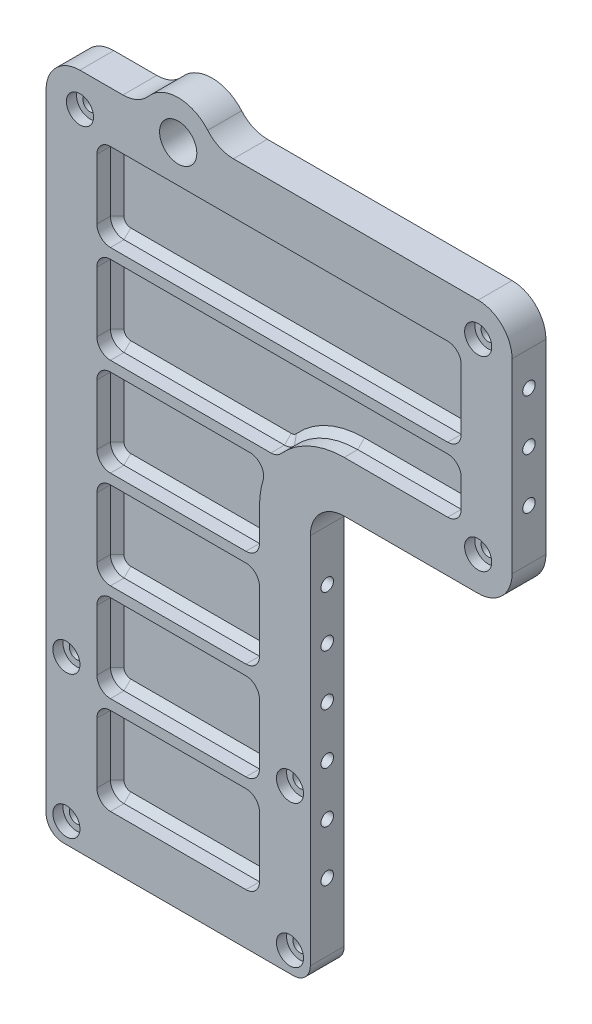
SolidWorks part; units mm, degrees
material "Petg 30% Infill"
ref_plane "Front Plane" through (0, 0, 0) normal (0, 0, 1) x (1, 0, 0)
ref_plane "Top Plane" through (0, 0, 0) normal (0, 1, 0) x (1, 0, 0)
ref_plane "Right Plane" through (0, 0, 0) normal (1, 0, 0) x (0, 0, -1)
sketch "Sketch1" plane through (0, 0, 0) normal (0, 0, 1) x (1, 0, 0)
  line L11 (-3.4368, 12.7092) -> (-3.4368, 122.7092)
  line L12 (6.5632, 132.7092) -> (46.1195, 132.7092)
  line L13 (56.1195, 142.7092) -> (56.1195, 197.7092)
  line L14 (46.1195, 207.7092) -> (-26.1197, 207.7092)
  line L15 (-58.754, 207.7092) -> (-71.4368, 207.7092)
  line L16 (-81.4368, 197.7092) -> (-81.4368, 12.7092)
  line L17 (-76.4368, 7.7092) -> (-8.4368, 7.7092)
  line L18 (-3.4368, 12.7092) -> (-3.4368, 122.7092)
  line L19 (6.5632, 132.7092) -> (46.1195, 132.7092)
  line L20 (56.1195, 142.7092) -> (56.1195, 197.7092)
  line L21 (46.1195, 207.7092) -> (-26.1197, 207.7092)
  line L22 (-58.754, 207.7092) -> (-71.4368, 207.7092)
  line L23 (-81.4368, 197.7092) -> (-81.4368, 12.7092)
  line L24 (-76.4368, 7.7092) -> (-8.4368, 7.7092)
  circle A0 centre (-42.4368, 203.7092) radius 5.5
  arc A1 (-3.4368, 12.7092) -> (-8.4368, 7.7092) centre (-8.4368, 12.7092) cw
  arc A2 (-81.4368, 12.7092) -> (-76.4368, 7.7092) centre (-76.4368, 12.7092) ccw
  circle A3 centre (-42.4368, 203.7092) radius 5.5 construction
  circle A4 centre (-75.4368, 55.7092) radius 2.15
  circle A5 centre (-75.4368, 13.7092) radius 2.15
  circle A6 centre (-9.4368, 13.7092) radius 2.15
  arc A7 (6.5632, 132.7092) -> (-3.4368, 122.7092) centre (6.5632, 122.7092) ccw
  arc A8 (46.1195, 132.7092) -> (56.1195, 142.7092) centre (46.1195, 142.7092) ccw
  arc A9 (56.1195, 197.7092) -> (46.1195, 207.7092) centre (46.1195, 197.7092) ccw
  arc A10 (-33.709, 211.1975) -> (-26.1197, 207.7092) centre (-26.1197, 217.7092) ccw
  arc A11 (-33.709, 211.1975) -> (-51.1646, 211.1975) centre (-42.4368, 203.7092) ccw
  arc A12 (-58.754, 207.7092) -> (-51.1646, 211.1975) centre (-58.754, 217.7092) ccw
  arc A13 (-71.4368, 207.7092) -> (-81.4368, 197.7092) centre (-71.4368, 197.7092) ccw
  arc A14 (6.5632, 132.7092) -> (-3.4368, 122.7092) centre (6.5632, 122.7092) ccw
  arc A15 (46.1195, 132.7092) -> (56.1195, 142.7092) centre (46.1195, 142.7092) ccw
  arc A16 (56.1195, 197.7092) -> (46.1195, 207.7092) centre (46.1195, 197.7092) ccw
  arc A17 (-33.709, 211.1975) -> (-26.1197, 207.7092) centre (-26.1197, 217.7092) ccw
  arc A18 (-33.709, 211.1975) -> (-51.1646, 211.1975) centre (-42.4368, 203.7092) ccw
  arc A19 (-58.754, 207.7092) -> (-51.1646, 211.1975) centre (-58.754, 217.7092) ccw
  arc A20 (-71.4368, 207.7092) -> (-81.4368, 197.7092) centre (-71.4368, 197.7092) ccw
  circle A21 centre (-9.4368, 55.7092) radius 2.15
  circle A23 centre (-75.4368, 13.7092) radius 2.2 construction
  circle A24 centre (-75.4368, 55.7092) radius 2.2 construction
  circle A25 centre (-9.4368, 13.7092) radius 2.2 construction
  circle A26 centre (-9.4368, 55.7092) radius 2.2 construction
  arc A35 (-81.4368, 12.7092) -> (-76.4368, 7.7092) centre (-76.4368, 12.7092) ccw
  arc A36 (-81.4368, 12.7092) -> (-76.4368, 7.7092) centre (-76.4368, 12.7092) ccw
  arc A37 (-8.4368, 7.7092) -> (-3.4368, 12.7092) centre (-8.4368, 12.7092) ccw
  arc A38 (-8.4368, 7.7092) -> (-3.4368, 12.7092) centre (-8.4368, 12.7092) ccw
  dimension "D2" = 4.3
  dimension "D3" = 5
  dimension "D1" = 0
extrude "Boss-Extrude1" add sketch "Sketch1" along normal blind 10 contours A1 L18 A14 L19 A15 L20 A16 L21 A17 A18 A19 L22 A20 L23 A2 L24 | A0 | A21 | A6 | A4 | A5
sketch "Sketch2" plane through (0, 0, 10) normal (0, 0, 1) x (1, 0, 0)
  circle A0 centre (-75.4368, 55.7092) radius 4
  circle A1 centre (-9.4368, 55.7092) radius 4
  circle A2 centre (-9.4368, 13.7092) radius 4
  circle A3 centre (-75.4368, 13.7092) radius 4
  dimension "D1" = 8
extrude "Cut-Extrude1" cut sketch "Sketch2" against normal blind 3
sketch "Sketch3" plane through (0, 0, 0) normal (0, 0, -1) x (-1, 0, 0)
  circle A0 centre (-21.6596, 190.973) radius 1.85
  circle A1 centre (31.0338, 190.3381) radius 1.85
  circle A2 centre (-21.6596, 190.973) radius 4.85
  circle A3 centre (31.0338, 190.3381) radius 4.85
  dimension "D1" = 3.7
  dimension "D2" = 3
extrude "Boss-Extrude2" add sketch "Sketch3" along normal blind 4
sketch "Sketch5" plane through (0, 0, 0) normal (0, 0, -1) x (-1, 0, 0)
  line L0 (47.5919, 184.6852) -> (47.5919, 70.4633) construction
  line L1 (13.3104, 85.2357) -> (47.5919, 85.2357)
  line L2 (13.3104, 85.2357) -> (13.3104, 70.4633)
  line L3 (13.3104, 70.4633) -> (47.5919, 70.4633)
  line L4 (47.5919, 85.2357) -> (47.5919, 70.4633)
  line L5 (47.5919, 70.4633) -> (-38.9159, 70.4633) construction
extrude "Boss-Extrude3" add sketch "Sketch5" along normal blind 4
sketch "Sketch6" plane through (0, 0, 0) normal (0, 0, -1) x (-1, 0, 0)
  line L0 (13.7834, 69.9633) -> (13.7834, 65.6705)
  line L1 (13.7834, 65.6705) -> (52.3848, 65.6705)
  line L2 (52.3848, 65.6705) -> (52.3848, 97.0706)
  line L3 (52.3848, 97.0706) -> (48.0919, 97.0706)
  line L4 (48.0919, 97.0706) -> (48.0919, 69.9633)
  line L5 (48.0919, 69.9633) -> (13.7834, 69.9633)
  line L6 (13.3104, 70.4633) -> (47.5919, 70.4633) construction
  line L7 (47.5919, 70.4633) -> (47.5919, 85.2357) construction
  dimension "D1" = 0.5
  dimension "D2" = 0.5
extrude "Boss-Extrude4" add sketch "Sketch6" along normal blind 6
sketch "Sketch7" plane through (0, 0, -6) normal (0, 0, -1) x (-1, 0, 0)
  line L0 (52.3848, 97.0706) -> (46.0919, 97.0706)
  line L1 (46.0919, 97.0706) -> (46.0919, 71.9633)
  line L2 (46.0919, 71.9633) -> (13.7834, 71.9633)
  line L3 (13.7834, 71.9633) -> (13.7834, 65.6705)
  line L4 (13.7834, 65.6705) -> (52.3848, 65.6705)
  line L5 (52.3848, 65.6705) -> (52.3848, 97.0706)
  line L6 (48.0919, 69.9633) -> (13.7834, 69.9633) construction
  dimension "D1" = 2
extrude "Boss-Extrude5" add sketch "Sketch7" along normal blind 2
chamfer "Chamfer1" distance 2 angle 45 2 edges at (-46.0919, 84.517, -6) (-29.9377, 71.9633, -6)
sketch "Sketch9" plane through (0, 0, 10) normal (0, 0, 1) x (1, 0, 0)
  circle A0 centre (-71.4368, 197.7092) radius 2.15
  circle A1 centre (46.1195, 197.7092) radius 2.15
  arc A2 (56.1195, 197.7092) -> (46.1195, 207.7092) centre (46.1195, 197.7092) ccw construction
  arc A3 (-71.4368, 207.7092) -> (-81.4368, 197.7092) centre (-71.4368, 197.7092) ccw construction
  circle A4 centre (46.1195, 142.7092) radius 2.15
  arc A5 (46.1195, 132.7092) -> (56.1195, 142.7092) centre (46.1195, 142.7092) ccw construction
  dimension "D1" = 4.3
extrude "Cut-Extrude3" cut sketch "Sketch9" against normal blind 20
sketch "Sketch10" plane through (0, 0, 10) normal (0, 0, 1) x (1, 0, 0)
  circle A0 centre (-71.4368, 197.7092) radius 4
  circle A1 centre (46.1195, 197.7092) radius 4
  circle A2 centre (46.1195, 197.7092) radius 2.15 construction
  circle A3 centre (46.1195, 142.7092) radius 4
  arc A4 (46.1195, 132.7092) -> (56.1195, 142.7092) centre (46.1195, 142.7092) ccw construction
  dimension "D1" = 8
extrude "Cut-Extrude4" cut sketch "Sketch10" against normal blind 3
chamfer "Chamfer2" distance 4 angle 45 2 edges at (16.8096, 190.973, 0) (-35.8838, 190.3381, 0)
sketch "Sketch12" plane through (0, 0, 10) normal (0, 0, 1) x (1, 0, 0)
  line L0 (-62.4368, 166.8758) -> (37.1195, 166.8758)
  line L1 (-62.4368, 163.8758) -> (37.1195, 163.8758)
  line L2 (-62.4368, 135.0425) -> (-21.2137, 135.0425)
  line L3 (-62.4368, 138.0425) -> (-15.0522, 138.0425)
  line L4 (-62.4368, 106.2092) -> (-22.4368, 106.2092)
  line L5 (-62.4368, 109.2092) -> (-22.4368, 109.2092)
  line L6 (-62.4368, 77.3758) -> (-22.4368, 77.3758)
  line L7 (-62.4368, 80.3758) -> (-22.4368, 80.3758)
  line L8 (-62.4368, 48.5425) -> (-22.4368, 48.5425)
  line L9 (-62.4368, 51.5425) -> (-22.4368, 51.5425)
  line L10 (-66.4368, 44.5425) -> (-66.4368, 26.7092)
  line L11 (-18.4368, 55.5425) -> (-18.4368, 73.3758)
  line L12 (-18.4368, 84.3758) -> (-18.4368, 102.2092)
  line L13 (-66.4368, 73.3758) -> (-66.4368, 55.5425)
  line L14 (-66.4368, 22.7092) -> (-18.4368, 22.7092)
  line L15 (-18.4368, 22.7092) -> (-18.4368, 122.7092)
  line L16 (6.5632, 147.7092) -> (41.1195, 147.7092)
  line L17 (41.1195, 147.7092) -> (41.1195, 192.7092)
  line L18 (41.1195, 192.7092) -> (-26.1197, 192.7092)
  line L19 (-58.754, 192.7092) -> (-66.4368, 192.7092)
  line L20 (-66.4368, 192.7092) -> (-66.4368, 22.7092)
  line L21 (-62.4368, 22.7092) -> (-22.4368, 22.7092)
  line L22 (-18.4368, 26.7092) -> (-18.4368, 44.5425)
  line L23 (6.5632, 147.7092) -> (37.1195, 147.7092)
  line L24 (41.1195, 151.7092) -> (41.1195, 159.8758)
  line L26 (37.1195, 192.7092) -> (-62.4368, 192.7092)
  line L27 (-66.4368, 188.7092) -> (-66.4368, 170.8758)
  line L28 (-18.4368, 113.2092) -> (-18.4368, 122.7092)
  line L29 (-66.4368, 102.2092) -> (-66.4368, 84.3758)
  line L30 (-66.4368, 131.0425) -> (-66.4368, 113.2092)
  line L31 (-66.4368, 159.8758) -> (-66.4368, 142.0425)
  line L32 (41.1195, 170.8758) -> (41.1195, 188.7092)
  line L33 (-38.7787, 192.7092) -> (-38.7787, 166.8758) construction
  line L34 (-38.7787, 166.8758) -> (-38.7787, 163.8758) construction
  line L35 (-38.7787, 163.8758) -> (-38.7787, 138.0425) construction
  line L36 (-38.7787, 138.0425) -> (-38.7787, 135.0425) construction
  line L37 (-38.7787, 135.0425) -> (-38.7787, 109.2092) construction
  line L38 (-38.7787, 109.2092) -> (-38.7787, 106.2092) construction
  line L39 (-38.7787, 106.2092) -> (-38.7787, 80.3758) construction
  line L40 (-38.7787, 80.3758) -> (-38.7787, 77.3758) construction
  line L41 (-38.7787, 77.3758) -> (-38.7787, 51.5425) construction
  line L42 (-38.7787, 51.5425) -> (-38.7787, 48.5425) construction
  line L43 (-38.7787, 48.5425) -> (-38.7787, 22.7092) construction
  arc A0 (-17.3824, 129.8931) -> (-18.4368, 122.7092) centre (6.5632, 122.7092) ccw
  arc A1 (-62.4368, 48.5425) -> (-66.4368, 44.5425) centre (-62.4368, 44.5425) ccw
  arc A2 (-22.4368, 48.5425) -> (-18.4368, 44.5425) centre (-22.4368, 44.5425) cw
  arc A3 (-22.4368, 51.5425) -> (-18.4368, 55.5425) centre (-22.4368, 55.5425) ccw
  arc A4 (-62.4368, 51.5425) -> (-66.4368, 55.5425) centre (-62.4368, 55.5425) cw
  arc A5 (-62.4368, 77.3758) -> (-66.4368, 73.3758) centre (-62.4368, 73.3758) ccw
  arc A6 (-22.4368, 77.3758) -> (-18.4368, 73.3758) centre (-22.4368, 73.3758) cw
  arc A7 (-62.4368, 22.7092) -> (-66.4368, 26.7092) centre (-62.4368, 26.7092) cw
  arc A8 (-22.4368, 22.7092) -> (-18.4368, 26.7092) centre (-22.4368, 26.7092) ccw
  arc A9 (37.1195, 147.7092) -> (41.1195, 151.7092) centre (37.1195, 151.7092) ccw
  arc A10 (41.1195, 188.7092) -> (37.1195, 192.7092) centre (37.1195, 188.7092) ccw
  arc A12 (-62.4368, 192.7092) -> (-66.4368, 188.7092) centre (-62.4368, 188.7092) ccw
  arc A13 (-22.4368, 80.3758) -> (-18.4368, 84.3758) centre (-22.4368, 84.3758) ccw
  arc A14 (6.5632, 147.7092) -> (-18.4368, 122.7092) centre (6.5632, 122.7092) ccw
  arc A15 (-42.4368, 198.7685) -> (-26.1197, 192.7092) centre (-26.1197, 217.7092) ccw
  arc A16 (-58.754, 192.7092) -> (-42.4368, 198.7685) centre (-58.754, 217.7092) ccw
  arc A17 (6.5632, 147.7092) -> (-12.0707, 139.3758) centre (6.5632, 122.7092) ccw
  arc A18 (-62.4368, 80.3758) -> (-66.4368, 84.3758) centre (-62.4368, 84.3758) cw
  arc A19 (-62.4368, 106.2092) -> (-66.4368, 102.2092) centre (-62.4368, 102.2092) ccw
  arc A20 (-22.4368, 106.2092) -> (-18.4368, 102.2092) centre (-22.4368, 102.2092) cw
  arc A21 (-22.4368, 109.2092) -> (-18.4368, 113.2092) centre (-22.4368, 113.2092) ccw
  arc A22 (-62.4368, 109.2092) -> (-66.4368, 113.2092) centre (-62.4368, 113.2092) cw
  arc A23 (-62.4368, 135.0425) -> (-66.4368, 131.0425) centre (-62.4368, 131.0425) ccw
  arc A24 (-21.2137, 135.0425) -> (-17.3824, 129.8931) centre (-21.2137, 131.0425) cw
  arc A25 (-15.0522, 138.0425) -> (-12.0707, 139.3758) centre (-15.0522, 142.0425) ccw
  arc A26 (-62.4368, 138.0425) -> (-66.4368, 142.0425) centre (-62.4368, 142.0425) cw
  arc A27 (-62.4368, 163.8758) -> (-66.4368, 159.8758) centre (-62.4368, 159.8758) ccw
  arc A28 (37.1195, 163.8758) -> (41.1195, 159.8758) centre (37.1195, 159.8758) cw
  arc A29 (37.1195, 166.8758) -> (41.1195, 170.8758) centre (37.1195, 170.8758) ccw
  arc A30 (-62.4368, 166.8758) -> (-66.4368, 170.8758) centre (-62.4368, 170.8758) cw
  point P47 (-66.4368, 48.5425)
  point P55 (-18.4368, 51.5425)
  point P60 (-66.4368, 77.3758)
  point P63 (-18.4368, 77.3758)
  point P66 (-18.4368, 80.3758)
  point P71 (-66.4368, 106.2092)
  point P74 (-18.4368, 106.2092)
  point P77 (-18.4368, 109.2092)
  point P82 (-66.4368, 135.0425)
  point P85 (-15.1828, 135.0425)
  point P92 (-66.4368, 163.8758)
  point P97 (41.1195, 166.8758)
  dimension "D3" = 3
  dimension "D7" = 4
  dimension "D1" = 15
  dimension "D5" = 5
extrude "Cut-Extrude5" cut sketch "Sketch12" against normal blind 6
chamfer "Chamfer3" distance 2 angle 45 52 edges at (41.1195, 179.7925, 4) (39.9479, 168.0474, 4) (-12.6587, 166.8758, 4) (-65.2653, 168.0474, 4) (-66.4368, 179.7925, 4) (-65.2653, 191.5376, 4) (-12.6587, 192.7092, 4) (39.9479, 191.5376, 4) (21.8413, 147.7092, 4) (-3.643, 145.5309, 4) (-13.4192, 138.391, 4) (-38.7445, 138.0425, 4) (-65.2653, 139.2141, 4) (-66.4368, 150.9592, 4) (-65.2653, 162.7042, 4) (-12.6587, 163.8758, 4) (39.9479, 162.7042, 4) (41.1195, 155.7925, 4) (39.9479, 148.8807, 4) (-18.4368, 117.9592, 4) (-19.6084, 110.3807, 4) (-42.4368, 109.2092, 4) (-65.2653, 110.3807, 4) (-66.4368, 122.1258, 4) (-65.2653, 133.8709, 4) (-41.8253, 135.0425, 4) (-18.0045, 133.4302, 4) (-18.1718, 126.3396, 4) (-42.4368, 80.3758, 4) (-65.2653, 81.5474, 4) (-66.4368, 93.2925, 4) (-65.2653, 105.0376, 4) (-42.4368, 106.2092, 4) (-19.6084, 105.0376, 4) (-18.4368, 93.2925, 4) (-19.6084, 81.5474, 4) (-42.4368, 51.5425, 4) (-65.2653, 52.7141, 4) (-66.4368, 64.4592, 4) (-65.2653, 76.2042, 4) (-42.4368, 77.3758, 4) (-19.6084, 76.2042, 4) (-18.4368, 64.4592, 4) (-19.6084, 52.7141, 4) (-42.4368, 48.5425, 4) (-19.6084, 47.3709, 4) (-18.4368, 35.6258, 4) (-19.6084, 23.8807, 4) (-42.4368, 22.7092, 4) (-65.2653, 23.8807, 4) (-66.4368, 35.6258, 4) (-65.2653, 47.3709, 4)
sketch "Sketch13" plane through (-3.4368, 0, 0) normal (1, 0, 0) x (0, 0, -1)
  line L0 (-10, 7.7092) -> (0, 7.7092) construction
  line L1 (-10, 12.7092) -> (0, 12.7092) construction
  circle A0 centre (-5, 32.7092) radius 1.85
  circle A1 centre (-5, 47.7092) radius 1.85
  circle A2 centre (-5, 62.7092) radius 1.85
  circle A3 centre (-5, 77.7092) radius 1.85
  circle A4 centre (-5, 92.7092) radius 1.85
  circle A5 centre (-5, 107.7092) radius 1.85
  point P6 (-5, 12.7092)
  dimension "D2" = 3.7
  dimension "D1" = 25
  dimension "D3" = 6
extrude "Cut-Extrude6" cut sketch "Sketch13" against normal blind 13
sketch "Sketch14" plane through (-81.4368, 0, 0) normal (-1, 0, 0) x (0, 0, 1)
  line L0 (10, 12.7092) -> (0, 12.7092) construction
  line L1 (10, 7.7092) -> (0, 7.7092) construction
  circle A0 centre (5, 32.7092) radius 1.85
  circle A1 centre (5, 47.7092) radius 1.85
  circle A2 centre (5, 62.7092) radius 1.85
  circle A3 centre (5, 77.7092) radius 1.85
  circle A4 centre (5, 92.7092) radius 1.85
  circle A5 centre (5, 107.7092) radius 1.85
  circle A6 centre (5, 122.7092) radius 1.85
  circle A7 centre (5, 137.7092) radius 1.85
  circle A8 centre (5, 152.7092) radius 1.85
  circle A9 centre (5, 167.7092) radius 1.85
  circle A10 centre (5, 182.7092) radius 1.85
  point P5 (5, 12.7092)
  dimension "D1" = 3.7
  dimension "D2" = 25
  dimension "D3" = 11
extrude "Cut-Extrude7" cut sketch "Sketch14" against normal blind 13
sketch "Sketch15" plane through (56.1195, 0, 0) normal (1, 0, 0) x (0, 0, -1)
  line L0 (-10, 197.7092) -> (0, 197.7092) construction
  line L1 (-10, 142.7092) -> (0, 142.7092) construction
  circle A0 centre (-5, 157.7092) radius 1.85
  circle A1 centre (-5, 172.7092) radius 1.85
  circle A2 centre (-5, 187.7092) radius 1.85
  point P4 (-5, 197.7092)
  point P11 (0, 0)
  dimension "D1" = 3.7
  dimension "D2" = 15
  dimension "D3" = 15
  dimension "D4" = 15
extrude "Cut-Extrude8" cut sketch "Sketch15" against normal blind 13
